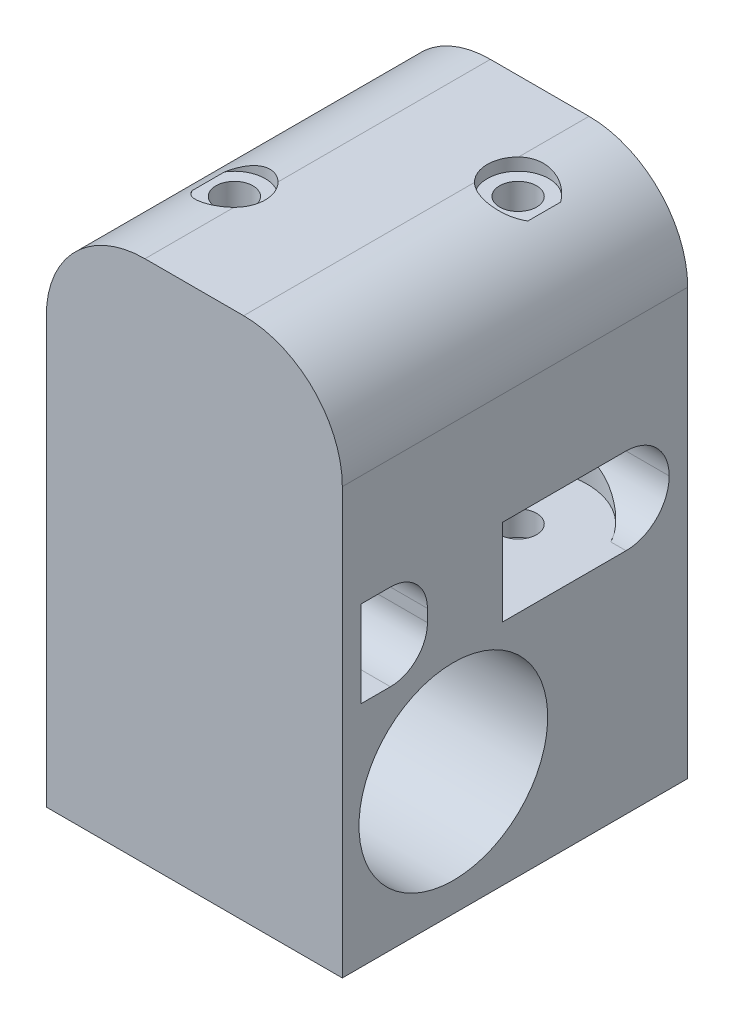
SolidWorks part; units mm, degrees
ref_plane "前视基准面" through (0, 0, 0) normal (0, 0, 1) x (1, 0, 0)
ref_plane "上视基准面" through (0, 0, 0) normal (0, 1, 0) x (1, 0, 0)
ref_plane "右视基准面" through (0, 0, 0) normal (1, 0, 0) x (0, 0, -1)
sketch "草图1" plane through (0, 0, 0) normal (0, 0, 1) x (1, 0, 0)
  line L1 (-12, 18) -> (12, 18)
  line L2 (-12, 18) -> (-12, -18)
  line L3 (-12, -18) -> (12, -18)
  line L4 (12, 18) -> (12, -18)
  line L5 (-12, 18) -> (12, -18) construction
  line L6 (-12, -18) -> (12, 18) construction
  point P0 (0, 0)
  dimension "D1" = 24
  dimension "D2" = 36
extrude "凸台-拉伸1" add sketch "草图1" along normal mid plane 38
ref_plane "基准面1" through (0, 3.5, 0) normal (0, 1, 0) x (1, 0, 0)
ref_plane "基准面2" through (0, -3.5, 0) normal (0, 1, 0) x (1, 0, 0)
sketch "草图3" plane through (0, 3.5, 0) normal (0, 1, 0) x (1, 0, 0)
  line L0 (0, 0) -> (0, -24.6721) construction
  line L1 (0, 0) -> (-19.2514, 0) construction
  line L2 (-5.75, -7.5) -> (-12, -7.5)
  line L3 (-12, -19) -> (-12, 19) construction
  line L4 (-12, -7.5) -> (-12, 19)
  line L5 (-12, 19) -> (1.75, 19)
  line L6 (12, 19) -> (-12, 19) construction
  line L7 (1.75, 19) -> (1.75, 0)
  circle A2 centre (-5.75, 0) radius 6.5 construction
  circle A3 centre (-5.75, 0) radius 5 construction
  arc A4 (-5.75, -7.5) -> (1.75, 0) centre (-5.75, 0) ccw
  dimension "D1" = 13
  dimension "D2" = 10
  dimension "D3" = 5.75
  dimension "D4" = 15
extrude "切除-拉伸2" cut sketch "草图3" against normal mid plane 7
sketch "草图4" plane through (-12, 0, 0) normal (-1, 0, 0) x (0, 0, 1)
  line L0 (13.2, -3.5) -> (-13.2, -3.5) construction
  line L1 (2.1, 0) -> (7.5, 0)
  line L2 (2.1, 0) -> (2.1, -7)
  line L3 (2.1, -7) -> (7.5, -7)
  line L4 (7.5, 0) -> (7.5, -7)
  line L5 (2.1, 0) -> (7.5, -7) construction
  line L6 (2.1, -7) -> (7.5, 0) construction
  line L7 (0, 0) -> (0, -29.9749) construction
  circle A0 centre (0, -3.5) radius 5 construction
  circle A1 centre (0, -3.5) radius 6.5 construction
  point P0 (4.8, -3.5)
  dimension "D1" = 10
  dimension "D2" = 13
  dimension "D3" = 5.4
  dimension "D4" = 7
  dimension "D5" = 4.8
extrude "切除-拉伸3" cut sketch "草图4" against normal through all
sketch "草图5" plane through (0, -3.5, 0) normal (0, 1, 0) x (1, 0, 0)
  line L0 (0, 0) -> (0, 26.819) construction
  line L1 (0, 0) -> (24.2805, 0) construction
  line L2 (0, 6.5) -> (23.2538, 6.5) construction
  line L3 (5.75, 4) -> (12, 4)
  line L4 (12, -19) -> (12, 19) construction
  line L5 (-1.75, 11.5) -> (-1.75, 19)
  line L6 (-12, 19) -> (12, 19) construction
  line L7 (-1.75, 19) -> (12, 19)
  line L8 (12, 19) -> (12, 4)
  circle A0 centre (5.75, 11.5) radius 5 construction
  circle A1 centre (5.75, 11.5) radius 6.5 construction
  arc A2 (-1.75, 11.5) -> (5.75, 4) centre (5.75, 11.5) ccw
  dimension "D2" = 10
  dimension "D3" = 13
  dimension "D5" = 15
  dimension "D1" = 6.5
  dimension "D4" = 5.75
extrude "切除-拉伸4" cut sketch "草图5" against normal mid plane 7
sketch "草图6" plane through (0, 0, -19) normal (0, 0, -1) x (-1, 0, 0)
  line L0 (0, 0) -> (0, 34.6715) construction
  line L1 (0, 0) -> (21.1433, 0) construction
  line L4 (-1.75, 7) -> (5.75, 7) construction
  circle A0 centre (0, 12) radius 4.15
  circle A1 centre (0, -12) radius 4.15
  point P2 (0, 22.7298)
  point P6 (0, 22.7298)
  dimension "D1" = 8.3
  dimension "D2" = 0
  dimension "D3" = 5
extrude "切除-拉伸5" cut sketch "草图6" against normal through all
fillet "圆角2" radius 3 2 edges at (0, -7, 2.1) (6.725, 0, 2.1)
sketch "草图10" plane through (12, 0, 0) normal (1, 0, 0) x (0, 0, -1)
  line L0 (-19, -18) -> (19, -18) construction
  line L1 (-9, -18) -> (-19, -18)
  line L2 (-9, -18) -> (-9, 18)
  line L3 (-9, 18) -> (-19, 18)
  line L4 (-19, -18) -> (-19, 18)
  dimension "D1" = 9
extrude "切除-拉伸9" cut sketch "草图10" against normal through all
sketch "草图11" plane through (-12, 0, 0) normal (-1, 0, 0) x (0, 0, 1)
  line L0 (0, 0) -> (0, -37.9964) construction
  line L2 (-19, -18) -> (9, -18)
  line L3 (9, -18) -> (9, -34.5)
  line L4 (9, -34.5) -> (-19, -34.5)
  line L5 (-19, -34.5) -> (-19, -18)
  dimension "D3" = 16.5
extrude "凸台-拉伸3" add sketch "草图11" against normal up to surface (24 mm away) up to face at (12, -3.5, 4.6929)
mirror "镜向2" about plane through (0, 0, 0) normal (0, 1, 0) of "凸台-拉伸3"
sketch "草图12" plane through (0, 0, 0) normal (0, 1, 0) x (1, 0, 0)
  line L0 (1.75, 0) -> (1.75, 28.6851) construction
  line L1 (-5.75, 5) -> (8.3291, 5) construction
  line L2 (-12, 19) -> (-1.75, 19)
  line L3 (12, 19) -> (-12, 19) construction
  line L4 (-1.75, 19) -> (-1.75, 7)
  line L5 (-1.75, 7) -> (-12, 7)
  line L6 (-0.75, 0) -> (-0.75, 28.6851) construction
  line L7 (-12, 19) -> (-12, -9) construction
  line L8 (-12, 7) -> (-12, 19)
  circle A0 centre (-5.75, 0) radius 7.5 construction
  arc A1 (1.45, -2.1) -> (1.75, 0) centre (-5.75, 0) ccw construction
  circle A2 centre (-5.75, 0) radius 6.5 construction
  circle A3 centre (-5.75, 0) radius 5 construction
  dimension "D1" = 13
  dimension "D2" = 10
  dimension "D3" = 1
  dimension "D4" = 2
extrude "凸台-拉伸4" add sketch "草图12" along normal up to surface (7 mm away) up to face at (-4.9393, 7, -4.2893)
fillet "圆角3" radius 3.5 2 edges at (-6.875, 0, -7) (-6.875, 7, -7)
sketch "草图13" plane through (0, 0, 0) normal (0, -1, 0) x (1, 0, 0)
  line L0 (12, -19) -> (1.75, -19)
  line L1 (12, -19) -> (-12, -19) construction
  line L2 (1.75, -19) -> (1.75, -17.5)
  line L3 (1.75, -17.5) -> (12, -17.5)
  line L4 (12, 9) -> (12, -19) construction
  line L5 (12, -17.5) -> (12, -19)
  line L7 (1.75, 0) -> (1.75, -5.1557) construction
  line L8 (5.75, -16.5) -> (17.8061, -16.5) construction
  circle A0 centre (5.75, -11.5) radius 7.5 construction
  arc A1 (5.75, -4) -> (1.75, -5.1557) centre (5.75, -11.5) ccw construction
  circle A2 centre (5.75, -11.5) radius 6.5 construction
  circle A3 centre (5.75, -11.5) radius 5 construction
  dimension "D1" = 10
  dimension "D2" = 13
  dimension "D3" = 0
  dimension "D4" = 1
extrude "凸台-拉伸5" add sketch "草图13" along normal up to surface (7 mm away) up to face at (4.9393, -7, -11.1893)
fillet "圆角4" radius 3.5 2 edges at (6.875, 0, -17.5) (6.875, -7, -17.5)
sketch "草图14" plane through (0, 0, 0) normal (0, -1, 0) x (1, 0, 0)
  circle A0 centre (5.75, -11.5) radius 5.6
  arc A1 (5.75, -4) -> (1.75, -5.1557) centre (5.75, -11.5) ccw construction
  dimension "D1" = 11.2
extrude "切除-拉伸10" cut sketch "草图14" along normal up to surface (7 mm away) up to face at (4.0281, -7, -11.9924)
fillet "圆角6" radius 3 1 edges at (-5.275, 0, 2.1)
sketch "草图16" plane through (0, 0, 9) normal (0, 0, 1) x (1, 0, 0)
  circle A0 centre (0, -12) radius 4.15 construction
  circle A1 centre (0, 12) radius 4.15 construction
  circle A2 centre (0, -12) radius 4.15
  circle A3 centre (0, 12) radius 4.15
extrude "凸台-拉伸6" add sketch "草图16" against normal blind 18
sketch "草图18" plane through (-12, 0, 0) normal (-1, 0, 0) x (0, 0, 1)
  line L0 (0, 0) -> (0, -26.1366) construction
  line L1 (7.5, -7) -> (-12.8032, -7) construction
  line L2 (-19, 34.5) -> (-19, -34.5) construction
  line L3 (-19, -25.5) -> (9, -25.5)
  line L4 (-19, -25.5) -> (-19, -34.5)
  line L5 (-19, -34.5) -> (9, -34.5)
  line L6 (9, -25.5) -> (9, -34.5)
  line L7 (-19, -34.5) -> (9, -34.5) construction
  line L8 (9, -34.5) -> (9, 34.5) construction
  line L9 (-19, 34.5) -> (9, 34.5)
  line L10 (-19, 34.5) -> (-19, 17)
  line L11 (-19, 17) -> (9, 17)
  line L12 (9, 34.5) -> (9, 17)
  line L13 (-3.5, 7) -> (7.5, 7) construction
  circle A0 centre (0, -15.5) radius 7.65
  dimension "D1" = 15.3
  dimension "D2" = 8.5
  dimension "D3" = 10
  dimension "D4" = 10
extrude "切除-拉伸11" cut sketch "草图18" against normal through all
fillet "圆角7" radius 8 2 edges at (-12, 17, -5) (12, 17, -5)
sketch "草图19" plane through (0, 17, 0) normal (0, 1, 0) x (1, 0, 0)
  circle A0 centre (5.75, 11.5) radius 1.5
  arc A2 (-1.75, 11.5) -> (5.75, 4) centre (5.75, 11.5) ccw construction
  dimension "D2" = 3
extrude "切除-拉伸12" cut sketch "草图19" against normal blind 26
sketch "草图20" plane through (0, 17, 0) normal (0, 1, 0) x (1, 0, 0)
  circle A0 centre (-5.75, 0) radius 1.5
  arc A1 (-5.75, -7.5) -> (1.75, 0) centre (-5.75, 0) ccw construction
  dimension "D1" = 3
extrude "切除-拉伸13" cut sketch "草图20" against normal blind 20
sketch "草图21" plane through (0, 17, 0) normal (0, 1, 0) x (1, 0, 0)
  circle A0 centre (5.75, 11.5) radius 2.5
  circle A1 centre (-5.75, 0) radius 2.5
  circle A2 centre (5.75, 11.5) radius 1.5 construction
  circle A3 centre (-5.75, 0) radius 1.5 construction
  dimension "D1" = 5
  dimension "D2" = 5
extrude "切除-拉伸14" cut sketch "草图21" against normal blind 1
